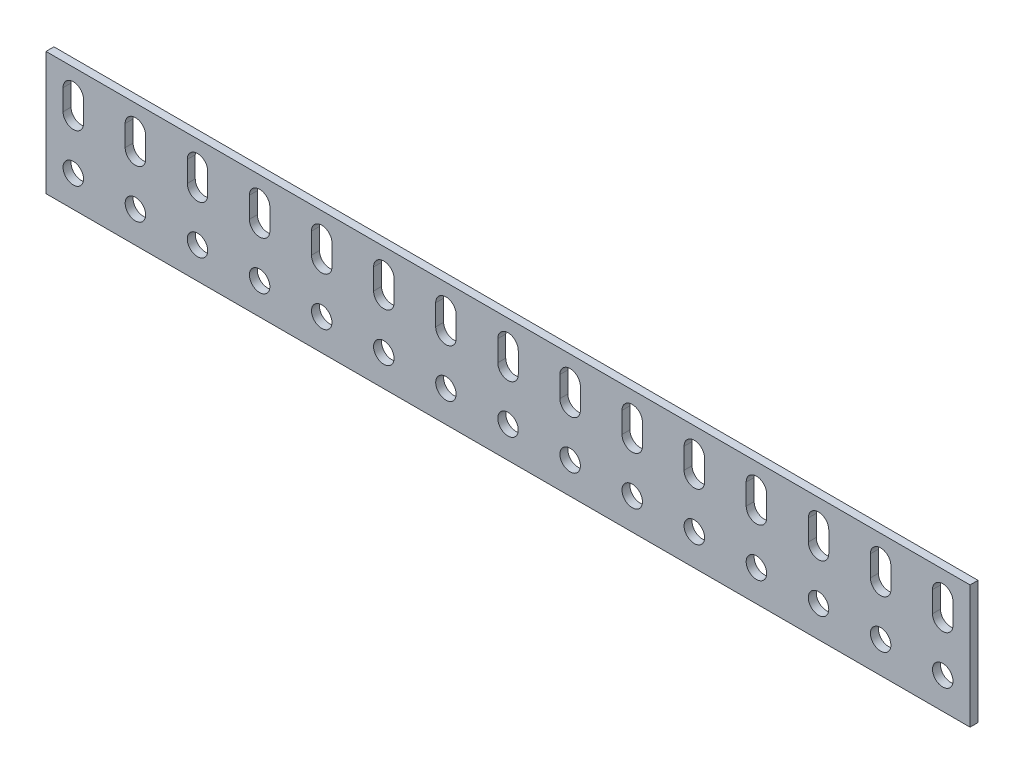
SolidWorks part; units mm, degrees
ref_plane "Front Plane" through (0, 0, 0) normal (0, 0, 1) x (1, 0, 0)
ref_plane "Top Plane" through (0, 0, 0) normal (0, 1, 0) x (1, 0, 0)
ref_plane "Right Plane" through (0, 0, 0) normal (1, 0, 0) x (0, 0, -1)
sketch "Sketch1" plane through (0, 0, 0) normal (0, 0, 1) x (1, 0, 0)
  line L4 (-147.648, 13.7425) -> (31.592, 13.7425) construction
  line L5 (-153.278, 32.6725) -> (37.222, 32.6725)
  line L6 (-153.278, 32.6725) -> (-153.278, 7.2725)
  line L7 (-153.278, 7.2725) -> (37.222, 7.2725)
  line L8 (37.222, 32.6725) -> (37.222, 7.2725)
  line L9 (31.592, 13.7425) -> (31.592, 32.6725) construction
  line L10 (31.592, 27.9625) -> (31.592, 23.6625) construction
  line L11 (33.702, 27.9625) -> (33.702, 23.6625)
  line L12 (29.482, 27.9625) -> (29.482, 23.6625)
  line L13 (-58.028, 32.6725) -> (-58.028, 7.2725) construction
  line L14 (18.7892, 27.9625) -> (18.7892, 23.6625) construction
  line L15 (20.8992, 27.9625) -> (20.8992, 23.6625)
  line L16 (16.6792, 27.9625) -> (16.6792, 23.6625)
  line L17 (5.9863, 27.9625) -> (5.9863, 23.6625) construction
  line L18 (8.0963, 27.9625) -> (8.0963, 23.6625)
  line L19 (3.8763, 27.9625) -> (3.8763, 23.6625)
  line L20 (-6.8165, 27.9625) -> (-6.8165, 23.6625) construction
  line L21 (-4.7065, 27.9625) -> (-4.7065, 23.6625)
  line L22 (-8.9265, 27.9625) -> (-8.9265, 23.6625)
  line L23 (-19.6194, 27.9625) -> (-19.6194, 23.6625) construction
  line L24 (-17.5094, 27.9625) -> (-17.5094, 23.6625)
  line L25 (-21.7294, 27.9625) -> (-21.7294, 23.6625)
  line L26 (-32.4222, 27.9625) -> (-32.4222, 23.6625) construction
  line L27 (-30.3122, 27.9625) -> (-30.3122, 23.6625)
  line L28 (-34.5322, 27.9625) -> (-34.5322, 23.6625)
  line L29 (-45.2251, 27.9625) -> (-45.2251, 23.6625) construction
  line L30 (-43.1151, 27.9625) -> (-43.1151, 23.6625)
  line L31 (-47.3351, 27.9625) -> (-47.3351, 23.6625)
  line L32 (-58.028, 27.9625) -> (-58.028, 23.6625) construction
  line L33 (-55.918, 27.9625) -> (-55.918, 23.6625)
  line L34 (-60.138, 27.9625) -> (-60.138, 23.6625)
  line L35 (-70.8308, 27.9625) -> (-70.8308, 23.6625) construction
  line L36 (-68.7208, 27.9625) -> (-68.7208, 23.6625)
  line L37 (-72.9408, 27.9625) -> (-72.9408, 23.6625)
  line L38 (-83.6337, 27.9625) -> (-83.6337, 23.6625) construction
  line L39 (-81.5237, 27.9625) -> (-81.5237, 23.6625)
  line L40 (-85.7437, 27.9625) -> (-85.7437, 23.6625)
  line L41 (-96.4365, 27.9625) -> (-96.4365, 23.6625) construction
  line L42 (-94.3265, 27.9625) -> (-94.3265, 23.6625)
  line L43 (-98.5465, 27.9625) -> (-98.5465, 23.6625)
  line L44 (-109.2394, 27.9625) -> (-109.2394, 23.6625) construction
  line L45 (-107.1294, 27.9625) -> (-107.1294, 23.6625)
  line L46 (-111.3494, 27.9625) -> (-111.3494, 23.6625)
  line L47 (-122.0422, 27.9625) -> (-122.0422, 23.6625) construction
  line L48 (-119.9322, 27.9625) -> (-119.9322, 23.6625)
  line L49 (-124.1522, 27.9625) -> (-124.1522, 23.6625)
  line L50 (-134.8451, 27.9625) -> (-134.8451, 23.6625) construction
  line L51 (-132.7351, 27.9625) -> (-132.7351, 23.6625)
  line L52 (-136.9551, 27.9625) -> (-136.9551, 23.6625)
  line L53 (-147.648, 27.9625) -> (-147.648, 23.6625) construction
  line L54 (-145.538, 27.9625) -> (-145.538, 23.6625)
  line L55 (-149.758, 27.9625) -> (-149.758, 23.6625)
  line L56 (31.592, 27.9625) -> (18.7892, 27.9625) construction
  line L57 (18.7892, 13.7425) -> (18.7892, 32.6725) construction
  circle A0 centre (-147.648, 13.7425) radius 2.11
  circle A1 centre (-134.8451, 13.7425) radius 2.11
  circle A2 centre (-122.0422, 13.7425) radius 2.11
  circle A3 centre (-109.2394, 13.7425) radius 2.11
  circle A4 centre (-96.4365, 13.7425) radius 2.11
  circle A5 centre (-83.6337, 13.7425) radius 2.11
  circle A6 centre (-70.8308, 13.7425) radius 2.11
  circle A7 centre (-58.028, 13.7425) radius 2.11
  circle A8 centre (-45.2251, 13.7425) radius 2.11
  circle A9 centre (-32.4222, 13.7425) radius 2.11
  circle A10 centre (-19.6194, 13.7425) radius 2.11
  circle A11 centre (-6.8165, 13.7425) radius 2.11
  circle A12 centre (5.9863, 13.7425) radius 2.11
  circle A13 centre (18.7892, 13.7425) radius 2.11
  circle A14 centre (31.592, 13.7425) radius 2.11
  arc A15 (33.702, 27.9625) -> (29.482, 27.9625) centre (31.592, 27.9625) ccw
  arc A16 (29.482, 23.6625) -> (33.702, 23.6625) centre (31.592, 23.6625) ccw
  arc A17 (20.8992, 27.9625) -> (16.6792, 27.9625) centre (18.7892, 27.9625) ccw
  arc A18 (16.6792, 23.6625) -> (20.8992, 23.6625) centre (18.7892, 23.6625) ccw
  arc A19 (8.0963, 27.9625) -> (3.8763, 27.9625) centre (5.9863, 27.9625) ccw
  arc A20 (3.8763, 23.6625) -> (8.0963, 23.6625) centre (5.9863, 23.6625) ccw
  arc A21 (-4.7065, 27.9625) -> (-8.9265, 27.9625) centre (-6.8165, 27.9625) ccw
  arc A22 (-8.9265, 23.6625) -> (-4.7065, 23.6625) centre (-6.8165, 23.6625) ccw
  arc A23 (-17.5094, 27.9625) -> (-21.7294, 27.9625) centre (-19.6194, 27.9625) ccw
  arc A24 (-21.7294, 23.6625) -> (-17.5094, 23.6625) centre (-19.6194, 23.6625) ccw
  arc A25 (-30.3122, 27.9625) -> (-34.5322, 27.9625) centre (-32.4222, 27.9625) ccw
  arc A26 (-34.5322, 23.6625) -> (-30.3122, 23.6625) centre (-32.4222, 23.6625) ccw
  arc A27 (-43.1151, 27.9625) -> (-47.3351, 27.9625) centre (-45.2251, 27.9625) ccw
  arc A28 (-47.3351, 23.6625) -> (-43.1151, 23.6625) centre (-45.2251, 23.6625) ccw
  arc A29 (-55.918, 27.9625) -> (-60.138, 27.9625) centre (-58.028, 27.9625) ccw
  arc A30 (-60.138, 23.6625) -> (-55.918, 23.6625) centre (-58.028, 23.6625) ccw
  arc A31 (-68.7208, 27.9625) -> (-72.9408, 27.9625) centre (-70.8308, 27.9625) ccw
  arc A32 (-72.9408, 23.6625) -> (-68.7208, 23.6625) centre (-70.8308, 23.6625) ccw
  arc A33 (-81.5237, 27.9625) -> (-85.7437, 27.9625) centre (-83.6337, 27.9625) ccw
  arc A34 (-85.7437, 23.6625) -> (-81.5237, 23.6625) centre (-83.6337, 23.6625) ccw
  arc A35 (-94.3265, 27.9625) -> (-98.5465, 27.9625) centre (-96.4365, 27.9625) ccw
  arc A36 (-98.5465, 23.6625) -> (-94.3265, 23.6625) centre (-96.4365, 23.6625) ccw
  arc A37 (-107.1294, 27.9625) -> (-111.3494, 27.9625) centre (-109.2394, 27.9625) ccw
  arc A38 (-111.3494, 23.6625) -> (-107.1294, 23.6625) centre (-109.2394, 23.6625) ccw
  arc A39 (-119.9322, 27.9625) -> (-124.1522, 27.9625) centre (-122.0422, 27.9625) ccw
  arc A40 (-124.1522, 23.6625) -> (-119.9322, 23.6625) centre (-122.0422, 23.6625) ccw
  arc A41 (-132.7351, 27.9625) -> (-136.9551, 27.9625) centre (-134.8451, 27.9625) ccw
  arc A42 (-136.9551, 23.6625) -> (-132.7351, 23.6625) centre (-134.8451, 23.6625) ccw
  arc A43 (-145.538, 27.9625) -> (-149.758, 27.9625) centre (-147.648, 27.9625) ccw
  arc A44 (-149.758, 23.6625) -> (-145.538, 23.6625) centre (-147.648, 23.6625) ccw
  point P8 (31.592, 25.8125)
  point P42 (0, 0)
  point P44 (31.592, 21.5525)
  point P45 (31.592, 30.0725)
  point P47 (0, 0)
  point P48 (33.702, 13.7425)
  point P49 (-58.028, 13.7425)
  point P50 (31.592, 11.6325)
  point P53 (18.7892, 25.8125)
  point P60 (5.9863, 25.8125)
  point P67 (-6.8165, 25.8125)
  point P74 (-19.6194, 25.8125)
  point P81 (-32.4222, 25.8125)
  point P88 (-45.2251, 25.8125)
  point P95 (-58.028, 25.8125)
  point P102 (-70.8308, 25.8125)
  point P109 (-83.6337, 25.8125)
  point P116 (-96.4365, 25.8125)
  point P123 (-109.2394, 25.8125)
  point P130 (-122.0422, 25.8125)
  point P137 (-134.8451, 25.8125)
  point P144 (-147.648, 25.8125)
  point P151 (0, 0)
  point P152 (0, 0)
  point P153 (0, 0)
  point P154 (0, 0)
  point P155 (0, 0)
  point P156 (0, 0)
  point P158 (0, 0)
  dimension "D3" = 8.52
  dimension "D5" = 12.8029
  dimension "D6" = 15
  dimension "D7" = 2.6
  dimension "D4" = 4.22
  dimension "D9" = 15
  dimension "D8" = 4.36
  dimension "D1" = 190.5
  dimension "D2" = 25.4
extrude "Boss-Extrude3" add sketch "Sketch1" along normal blind 1.64 contours L8 L7 L6 L5
extrude "Cut-Extrude8" cut sketch "Sketch1<9>" along normal blind 1.64 contours L19 A20 L18 A19 | L22 A22 L21 A21 | L25 A24 L24 A23 | L28 A26 L27 A25 | L31 A28 L30 A27 | L37 A32 L36 A31 | A14 | A13 | A12 | A11 | A10 | A9 | A8 | A6 | A5 | A3 | L43 A36 L42 A35 | L40 A34 L39 A33 | A2 | L52 A42 L51 A41 | A1 | L55 A44 L54 A43 | A0 | L11 A16 L12 A15 | L15 A18 L16 A17 | L33 A30 L34 A29 | A7 | A4 | L45 A38 L46 A37 | L48 A40 L49 A39 region at (5.9863, 25.8125, 0) region at (-6.8165, 25.8125, 0) region at (-19.6194, 25.8125, 0) region at (-32.4222, 25.8125, 0) region at (-45.2251, 25.8125, 0) region at (-70.8308, 25.8125, 0) region at (-83.6337, 25.8125, 0) region at (-96.4365, 25.8125, 0) region at (-134.8451, 25.8125, 0) region at (-147.648, 25.8125, 0) region at (-147.648, 13.7425, 0) region at (-134.8451, 13.7425, 0) region at (-122.0422, 13.7425, 0) region at (-109.2394, 13.7425, 0) region at (-83.6337, 13.7425, 0) region at (-70.8308, 13.7425, 0) region at (-45.2251, 13.7425, 0) region at (-32.4222, 13.7425, 0) region at (-19.6194, 13.7425, 0) region at (-6.8165, 13.7425, 0) region at (5.9863, 13.7425, 0) region at (18.7892, 13.7425, 0) region at (31.592, 13.7425, 0)
sketch "Sketch1<9>" plane through (0, 0, 0) normal (0, 0, 1) x (1, 0, 0) same geometry as "Sketch1"
